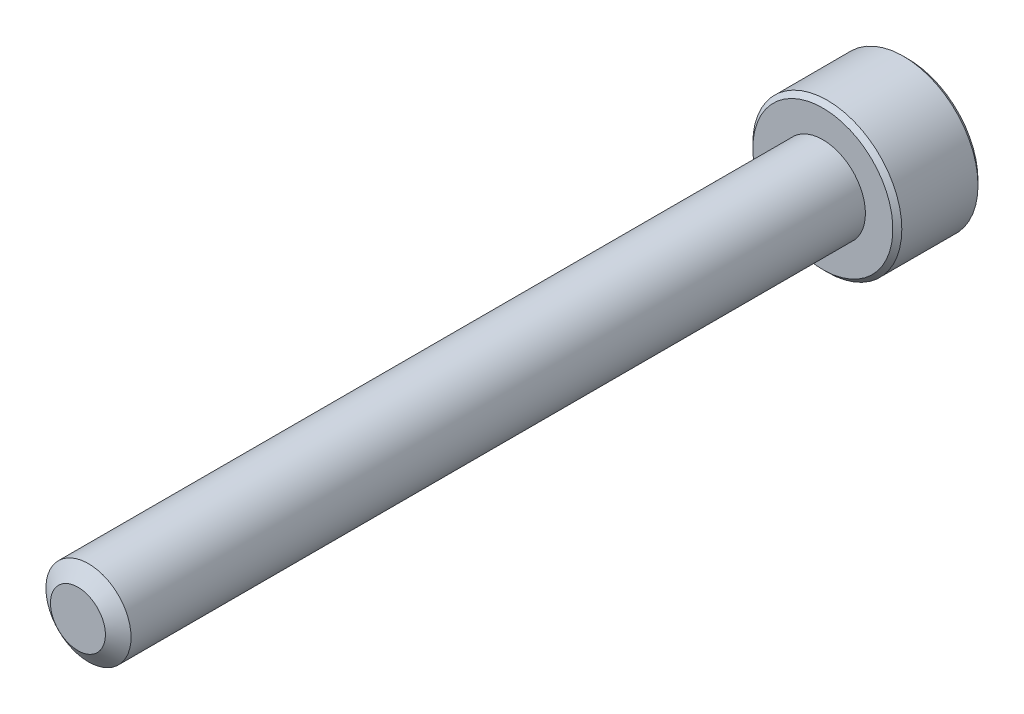
SolidWorks part; units mm, degrees
material "Alloy Steel"
ref_plane "Front Plane" through (0, 0, 0) normal (0, 0, 1) x (1, 0, 0)
ref_plane "Top Plane" through (0, 0, 0) normal (0, 1, 0) x (1, 0, 0)
ref_plane "Right Plane" through (0, 0, 0) normal (1, 0, 0) x (0, 0, -1)
sketch "Sketch1" plane through (0, 0, 0) normal (0, 0, 1) x (1, 0, 0)
  circle A0 centre (0, 0) radius 2
  dimension "OD" = 4
extrude "Extrude1" add sketch "Sketch1" against normal blind 35
sketch "Sketch2" plane through (0, 0, 0) normal (0, 0, 1) x (1, 0, 0)
  circle A0 centre (0, 0) radius 2 construction
  circle A1 centre (0, 0) radius 2
curve "Helix/Spiral1" [suppressed] pitch 0.7 height 35.7 turns 51 parameters "pitch"=0.7
sketch "Sketch3" plane through (0, 0, 0) normal (1, 0, 0) x (0, 0, -1)
  line L0 (-0.6125, 2) -> (-0.35, 1.5453)
  line L1 (-0.35, 1.5453) -> (-0.2625, 1.5453)
  line L2 (-0.2625, 1.5453) -> (0, 2)
  line L3 (-0.6125, 2) -> (0, 2)
  line L4 (-0.3063, 2) -> (-0.3063, 1.5453) construction
  line L5 (-0.4813, 1.7727) -> (-0.1313, 1.7727) construction
  line L6 (0, 2) -> (0, -2) construction
  line L7 (0, -2) -> (35, -2) construction
  point P11 (3.15, -2)
  dimension "D1" = 0.0875
  dimension "D2" = 0.35
  dimension "D3" = 60
  dimension "D4" = 3.15
sweep "Cut-Sweep1" [suppressed] cut profiles "Sketch3" path "Helix/Spiral1"
sketch "Sketch4" plane through (0, 0, 0) normal (1, 0, 0) x (0, 0, -1)
  line L0 (0.4962, 2) -> (0, 1.2913)
  line L1 (0, 1.2913) -> (0, 2)
  line L2 (0.4962, 2) -> (0, 2)
  line L3 (-0.6125, 2) -> (0, 2) construction
  line L4 (0, 0) -> (7.0209, 0) construction
  dimension "D1" = 55
  dimension "D2" = 0.254
revolve "Cut-Revolve1" cut sketch "Sketch4" angle 360 about L4
sketch "Sketch5" [suppressed] plane through (0, 0, 0) normal (1, 0, 0) x (0, 0, -1)
  line L0 (35, -1.5557) -> (35, 1.4271) construction
  line L1 (35, 2) -> (0.1203, 2)
  line L2 (35, 2) -> (35, 0)
  line L3 (35, 0) -> (0.0001, 0)
  line L4 (0.0001, 1.6698) -> (0.0001, 0)
  line L5 (0.1203, 2) -> (0.0001, 1.6698)
  line L6 (0, 0) -> (9.9695, 0) construction
  point P3 (0.0001, 2)
  point P10 (0.0001, 2)
  dimension "D1" = 0.3302
  dimension "Thread min" = 0.0001
  dimension "D3" = 20
revolve "partially thread" [suppressed] add sketch "Sketch5" angle 360 about L6
sketch "Sketch6" plane through (0, 0, -35) normal (0, 0, -1) x (-1, 0, 0)
  circle A0 centre (0, 0) radius 3.5
  dimension "head dia" = 7
extrude "Extrude2" add sketch "Sketch6" along normal blind 4
sketch "Sketch7" plane through (0, 0, -39) normal (0, 0, -1) x (-1, 0, 0)
  line L1 (0, 1.7321) -> (-1.5, 0.866)
  line L2 (-1.5, 0.866) -> (-1.5, -0.866)
  line L3 (-1.5, -0.866) -> (0, -1.7321)
  line L4 (0, -1.7321) -> (1.5, -0.866)
  line L5 (1.5, -0.866) -> (1.5, 0.866)
  line L6 (1.5, 0.866) -> (0, 1.7321)
  circle A0 centre (0, 0) radius 1.5 construction
  dimension "hex dia" = 3
extrude "Cut-Extrude1" cut sketch "Sketch7" against normal blind 2.25
sketch "Sketch8" plane through (0, 0, -39) normal (0, 0, -1) x (-1, 0, 0)
  circle A0 centre (0, 0) radius 1.7321
extrude "Cut-Extrude2" cut sketch "Sketch8" against normal through all draft 45
chamfer "Chamfer1" distance 0.21 angle 45 2 edges at (-3.5, 0, -39) (-3.5, 0, -35)
sketch "Sketch9" plane through (0, 0, 0) normal (1, 0, 0) x (0, 0, -1)
  line L0 (0, 2) -> (0, -2) construction
  line L1 (3.85, 2) -> (3.85, -2) construction
  dimension "D1" = 3.85
sketch "Sketch10" plane through (0, 0, 0) normal (1, 0, 0) x (0, 0, -1)
  line L0 (35, 2) -> (35, 0)
  line L1 (35, 2) -> (34.825, 2)
  line L2 (34.825, 2) -> (33.9966, 0)
  line L3 (35, 0) -> (33.9966, 0)
  line L4 (35, 3.29) -> (35, -3.29) construction
  dimension "D1" = 22.5
  dimension "D2" = 0.175
revolve "Revolve1" add sketch "Sketch10" angle 360 about L3
equation "\"D3@Helix/Spiral1\" = \"screw length@Extrude1\"+\"pitch@Helix/Spiral1\""
equation "\"D1@Sketch3\" = \"pitch@Helix/Spiral1\"*.125"
equation "\"D2@Sketch3\" = \"pitch@Helix/Spiral1\"*.5"
equation "\"D1@Cut-Extrude1\" = \"hex dia@Sketch7\"*.75"
equation "\"D1@Chamfer1\" = \"head dia@Sketch6\"*.03"
equation "\"D1@Sketch9\" = \"pitch@Helix/Spiral1\"*5.5"
equation "\"D2@Sketch10\" = \"pitch@Helix/Spiral1\"*.25"
equation "\"D4@Sketch3\" = \"pitch@Helix/Spiral1\"*4.50"
